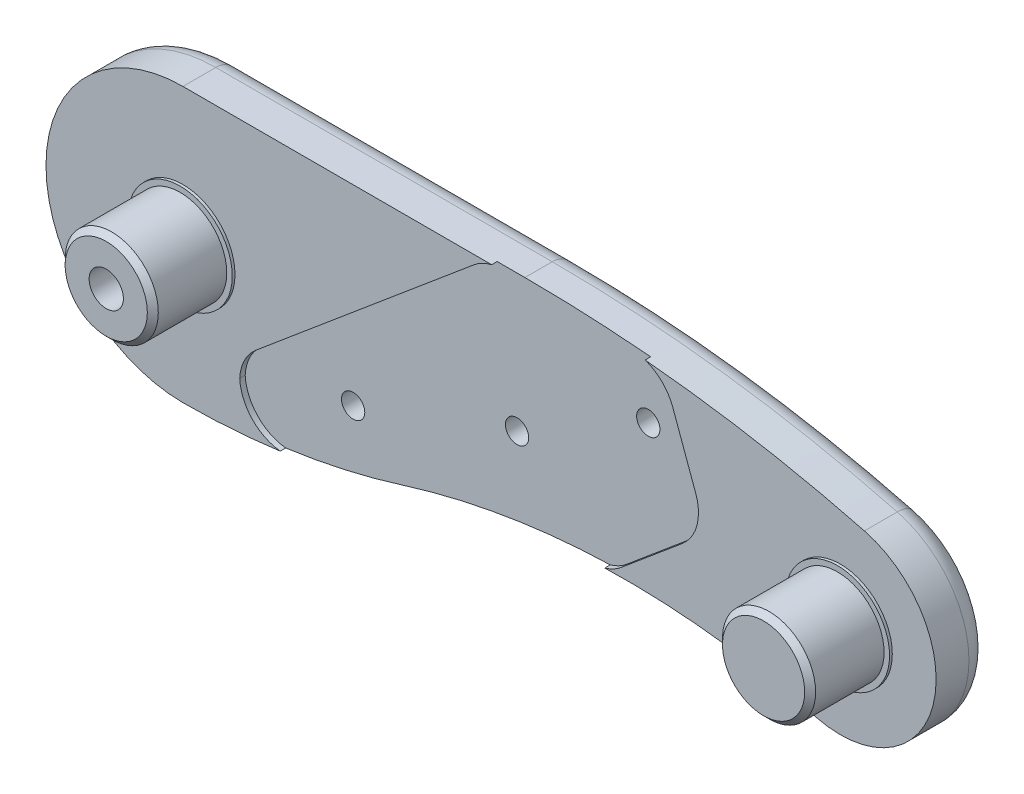
SolidWorks part; units mm, degrees
ref_plane "Front Plane" through (0, 0, 0) normal (0, 0, 1) x (1, 0, 0)
ref_plane "Top Plane" through (0, 0, 0) normal (0, 1, 0) x (1, 0, 0)
ref_plane "Right Plane" through (0, 0, 0) normal (1, 0, 0) x (0, 0, -1)
sketch "Sketch1" plane through (0, 0, 0) normal (0, 0, 1) x (1, 0, 0)
  line L0 (0, 25) -> (61.4231, 25)
  line L1 (0, 0) -> (120, 0) construction
  line L2 (0, 0) -> (0, -25) construction
  circle A0 centre (0, 0) radius 25
  circle A1 centre (120, 0) radius 17.5
  arc A2 (61.4231, 25) -> (124.409, 16.9355) centre (61.4231, -225) cw
  arc A3 (115.6605, -16.9534) -> (38.9734, -19.0205) centre (80.9448, -152.5809) ccw
  arc A4 (0, -25) -> (38.9734, -19.0205) centre (0, 105) ccw
  dimension "D1" = 50
  dimension "D3" = 35
  dimension "D4" = 130
  dimension "D5" = 140
  dimension "D6" = 250
  dimension "D2" = 120
extrude "Boss-Extrude1" add sketch "Sketch1" along normal blind 6 contours A0 A4 A3 A1 A2 L0 | A0 | A1 region at (60.7118, 4.4003, 0) region at (0, 0, 0) region at (120, 0, 0)
sketch "Sketch3" plane through (0, 0, 0) normal (0, 0, -1) x (-1, 0, 0)
  circle A0 centre (0, 0) radius 11
  circle A1 centre (0, 0) radius 25
  arc A2 (0, -25) -> (0, 25) centre (0, 0) ccw construction
  line M1 (0, 25) -> (-61.4231, 25)
  arc M2 (-61.4231, 25) -> (-124.409, 16.9355) centre (-61.4231, -225) ccw
  arc M3 (-124.409, 16.9355) -> (-115.6605, -16.9534) centre (-120, 0) ccw
  arc M4 (-115.6605, -16.9534) -> (-38.9734, -19.0205) centre (-80.9448, -152.5809) cw
  arc M5 (-38.9734, -19.0205) -> (0, -25) centre (0, 105) ccw
  arc M6 (0, -25) -> (0, 25) centre (0, 0) ccw
  dimension "D1" = 22
extrude "Boss-Extrude3" add sketch "Sketch3" along normal blind 4 contours A1 M1 M2 M3 M4 M5 | A1 A0 M6 region at (-17.1777, -17.1777, 0) region at (73.5538, 3.4472, 0)
sketch "Sketch4" plane through (0, 0, 6) normal (0, 0, 1) x (1, 0, 0)
  circle A0 centre (0, 0) radius 8.5
  circle A1 centre (120, 0) radius 8.5
  dimension "D1" = 17
  dimension "D2" = 17
extrude "Boss-Extrude4" add sketch "Sketch4" along normal blind 14
sketch "Sketch5" plane through (0, 0, -4) normal (0, 0, -1) x (-1, 0, 0)
  line L0 (0, 0) -> (-60, 0) construction
  line L1 (0, 0) -> (-83.9535, 13.2969) construction
  line L2 (0, 0) -> (-30.0702, -10.9446) construction
  circle A0 centre (-83.9535, 13.2969) radius 2.125
  circle A1 centre (-60, 0) radius 2.125
  circle A2 centre (-30.0702, -10.9446) radius 2.125
  dimension "D6" = 4.25
  dimension "D1" = 20
  dimension "D2" = 9
  dimension "D3" = 85
  dimension "D4" = 60
  dimension "D5" = 32
extrude "Cut-Extrude1" cut sketch "Sketch5" against normal through all
sketch "Sketch6" plane through (0, 0, -4) normal (0, 0, -1) x (-1, 0, 0)
  circle A0 centre (-83.9535, 13.2969) radius 3.75
  circle A1 centre (-60, 0) radius 3.75
  circle A2 centre (-30.0702, -10.9446) radius 3.75
  dimension "D1" = 7.5
extrude "Cut-Extrude2" cut sketch "Sketch6" against normal blind 4.25
fillet "Fillet1" radius 4 6 edges at (-25, 0, -4) (19.7147, -23.4964, -4) (77.1726, -12.6318, -4) (136.9445, -4.3742, -4) (93.1732, 22.9757, -4) (30.7116, 25, -4)
sketch "Sketch7" plane through (0, 0, 6) normal (0, 0, 1) x (1, 0, 0)
  circle A0 centre (0, 0) radius 9.5
  circle A1 centre (0, 0) radius 8.5 construction
  circle A2 centre (120, 0) radius 9.5
  circle A3 centre (0, 0) radius 8.5
  circle A4 centre (0, 0) radius 8.5
  circle A5 centre (120, 0) radius 8.5 construction
  circle A6 centre (120, 0) radius 8.5
  dimension "D1" = 1
  dimension "D3" = 1
  dimension "D2" = 0
extrude "Boss-Extrude5" add sketch "Sketch7" along normal blind 0.5
chamfer "Chamfer2" distance 1 angle 45 2 edges at (8.5, 0, 20) (128.5, 0, 20)
sketch "Sketch8" plane through (0, 0, 0) normal (0, 0, -1) x (-1, 0, 0)
  circle A0 centre (0, 0) radius 1.625
  dimension "D1" = 3.25
extrude "Cut-Extrude3" cut sketch "Sketch8" against normal through all
sketch "Sketch9" plane through (0, 0, 20) normal (0, 0, 1) x (1, 0, 0)
  circle A0 centre (0, 0) radius 3.125
  dimension "D1" = 6.25
extrude "Cut-Extrude4" cut sketch "Sketch9" against normal blind 17
sketch "Sketch10" plane through (0, 0, 0) normal (0, 0, -1) x (-1, 0, 0)
  line L0 (0, 0) -> (0, 7.42) construction
  circle A0 centre (0, 0) radius 7.42 construction
  circle A1 centre (0, 7.42) radius 1
  circle A2 centre (7.42, 0) radius 1
  circle A3 centre (0, -7.42) radius 1
  circle A4 centre (-7.42, 0) radius 1
  point P14 (0, 0)
  dimension "D1" = 14.84
  dimension "D2" = 2
  dimension "D3" = 4
extrude "Cut-Extrude5" cut sketch "Sketch10" against normal blind 4
sketch "Sketch11" plane through (0, 0, -4) normal (0, 0, -1) x (-1, 0, 0)
  circle A0 centre (0, 0) radius 15
  circle A1 centre (0, 0) radius 11 construction
  circle A2 centre (0, 0) radius 11
  dimension "D1" = 4
extrude "Boss-Extrude6" add sketch "Sketch11" along normal blind 2
chamfer "Chamfer3" distance 4 angle 45 1 edges at (-15, 0, -4)
sketch "Sketch12" plane through (0, 0, 6) normal (0, 0, 1) x (1, 0, 0)
  line L0 (91.0061, -1.4841) -> (79.8556, -10.8405) construction
  line L1 (13.4637, -10.2418) -> (53.2327, 23.1284) construction
  line L2 (58.375, 25) -> (61.4231, 25) construction
  line L3 (93.3813, 7.3804) -> (89.1932, 18.8872) construction
  line L4 (91.0061, -1.4841) -> (79.8556, -10.8405)
  line L5 (13.4637, -10.2418) -> (53.2327, 23.1284)
  line L6 (58.375, 25) -> (61.4231, 25)
  line L7 (93.3813, 7.3804) -> (89.1932, 18.8872)
  line L8 (93.6163, 7.4659) -> (89.4281, 18.9727)
  line L9 (58.375, 25.25) -> (61.4231, 25.25)
  line L10 (13.303, -10.0503) -> (53.072, 23.3199)
  line L11 (91.1668, -1.6756) -> (80.0163, -11.032)
  arc A0 (10.6159, -15.9715) -> (19.8261, -23.4793) centre (18.606, -15.5729) ccw construction
  arc A1 (19.8261, -23.4793) -> (38.9734, -19.0205) centre (0, 105) ccw construction
  arc A2 (75.0501, -12.7051) -> (38.9734, -19.0205) centre (80.9448, -152.5809) ccw construction
  arc A3 (75.0501, -12.7051) -> (79.8556, -10.8405) centre (74.7133, -4.7122) ccw construction
  arc A4 (91.0061, -1.4841) -> (93.3813, 7.3804) centre (85.8638, 4.6442) ccw construction
  arc A5 (13.4637, -10.2418) -> (10.6159, -15.9715) centre (18.606, -16.3702) ccw construction
  arc A6 (58.375, 25) -> (53.2327, 23.1284) centre (58.375, 17) ccw construction
  arc A7 (82.3452, 24.123) -> (61.4231, 25) centre (61.4231, -225) ccw construction
  arc A8 (89.1932, 18.8872) -> (82.3452, 24.123) centre (81.6757, 16.1511) ccw construction
  arc A9 (10.6159, -15.9715) -> (19.8261, -23.4793) centre (18.606, -15.5729) ccw
  arc A10 (19.8261, -23.4793) -> (38.9734, -19.0205) centre (0, 105) ccw
  arc A11 (75.0501, -12.7051) -> (38.9734, -19.0205) centre (80.9448, -152.5809) ccw
  arc A12 (75.0501, -12.7051) -> (79.8556, -10.8405) centre (74.7133, -4.7122) ccw
  arc A13 (91.0061, -1.4841) -> (93.3813, 7.3804) centre (85.8638, 4.6442) ccw
  arc A14 (13.4637, -10.2418) -> (10.6159, -15.9715) centre (18.606, -16.3702) ccw
  arc A15 (58.375, 25) -> (53.2327, 23.1284) centre (58.375, 17) ccw
  arc A16 (82.3452, 24.123) -> (61.4231, 25) centre (61.4231, -225) ccw
  arc A17 (89.1932, 18.8872) -> (82.3452, 24.123) centre (81.6757, 16.1511) ccw
  arc A18 (91.1668, -1.6756) -> (93.6163, 7.4659) centre (85.8638, 4.6442) ccw
  arc A19 (89.4281, 18.9727) -> (82.3661, 24.3721) centre (81.6757, 16.1511) ccw
  arc A20 (82.3661, 24.3721) -> (61.4231, 25.25) centre (61.4231, -225) ccw
  arc A21 (58.375, 25.25) -> (53.072, 23.3199) centre (58.375, 17) ccw
  arc A22 (13.303, -10.0503) -> (10.3656, -15.9715) centre (18.606, -16.3702) ccw
  arc A23 (10.3656, -15.9715) -> (19.8642, -23.7264) centre (18.606, -15.5729) ccw
  arc A24 (19.8642, -23.7264) -> (39.0484, -19.259) centre (0, 105) ccw
  arc A25 (75.0606, -12.9549) -> (39.0484, -19.259) centre (80.9448, -152.5809) ccw
  arc A26 (75.0606, -12.9549) -> (80.0163, -11.032) centre (74.7133, -4.7122) ccw
  circle M15 centre (83.9535, 13.2969) radius 2.125
  circle M16 centre (60, 0) radius 2.125
  circle M17 centre (30.0702, -10.9446) radius 2.125
  line M18 (61.4231, 25) -> (0, 25)
  arc M20 (0, -25) -> (38.9734, -19.0205) centre (0, 105) ccw
  arc M21 (38.9734, -19.0205) -> (115.6605, -16.9534) centre (80.9448, -152.5809) cw
  arc M23 (124.409, 16.9355) -> (61.4231, 25) centre (61.4231, -225) ccw
  dimension "D1" = 0.25
extrude "Cut-Extrude6" cut sketch "Sketch12" against normal blind 1 contours L7 A17 A15 L5 A14 A9 A12 L4 A13 M23 M18 M20 M21 M15 M17 M16 | A26 L11 A18 L8 A19 A17 L7 A13 L4 A12 M21 M23 | A22 A23 A9 A14 L5 A15 A21 L10 M20 M18 | A25 A26 A23 A24 M21 M20 region at (93.6313, 2.5629, 6) region at (55.4794, 1.0069, 6) region at (76.0317, -12.7275, 6) region at (12.6681, -21.2013, 6)
